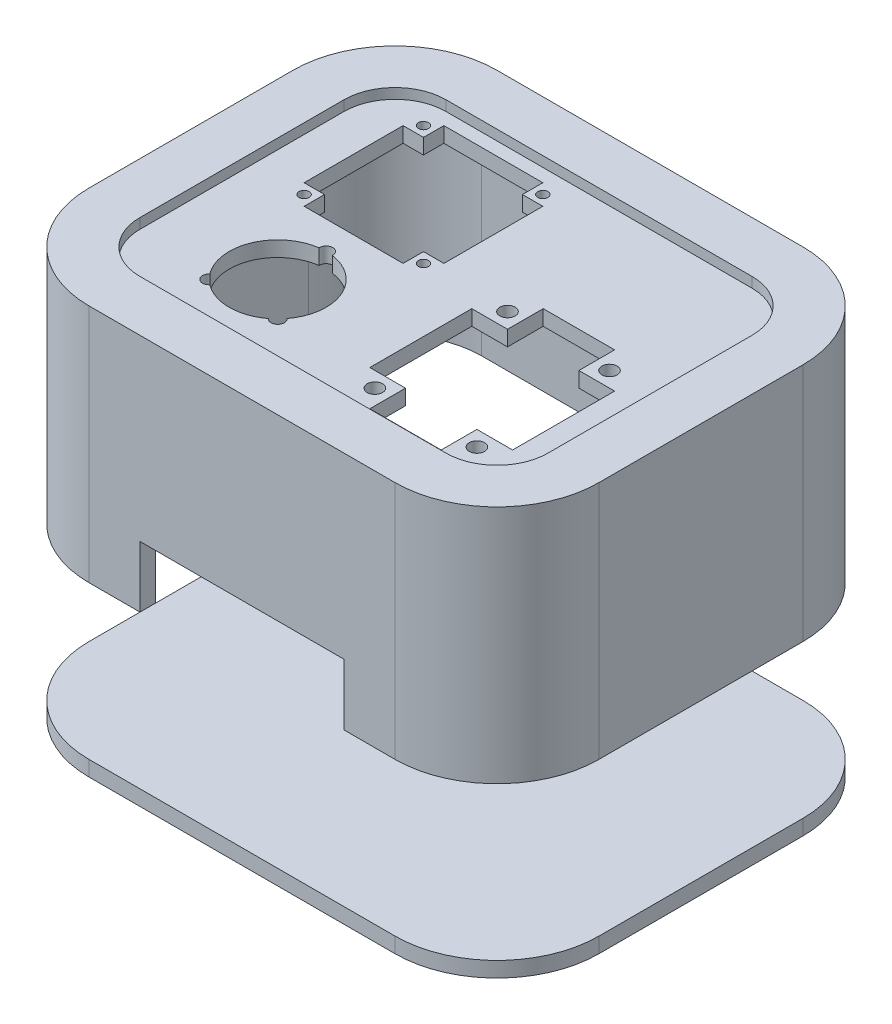
SolidWorks part; units mm, degrees
note: The reader was unsure of these and kept them because the rebuilt part matched: shared geometry of "草图2<6>", "草图2<8>", "草图9<7>", "草图9<8>", "草图9<9>", "草图9<10>", "草图9<11>", "草图9<12>", "草图9<13>".
ref_plane "前视基准面" through (0, 0, 0) normal (0, 0, 1) x (1, 0, 0)
ref_plane "上视基准面" through (0, 0, 0) normal (0, 1, 0) x (1, 0, 0)
ref_plane "右视基准面" through (0, 0, 0) normal (1, 0, 0) x (0, 0, -1)
sketch "草图1" plane through (0, 0, 0) normal (0, 1, 0) x (1, 0, 0)
  line L0 (10, 0) -> (70, 0)
  line L1 (80, 10) -> (80, 50)
  line L2 (70, 60) -> (10, 60)
  line L3 (0, 50) -> (0, 10)
  arc A0 (0, 50) -> (10, 60) centre (10, 50) cw
  arc A1 (80, 50) -> (70, 60) centre (70, 50) ccw
  arc A2 (70, 0) -> (80, 10) centre (70, 10) ccw
  arc A3 (10, 0) -> (0, 10) centre (10, 10) cw
  point P7 (0, 60)
  point P12 (80, 0)
  point P15 (0, 0)
  dimension "D3" = 10
  dimension "D4" = 10
  dimension "D5" = 10
  dimension "D6" = 10
  dimension "D1" = 80
  dimension "D2" = 60
extrude "拉伸-薄壁1" add sketch "草图1" along normal blind 60 thin contours L3 A3 L0 A2 L1 A1 L2 A0
sketch "草图2" plane through (0, 60, 0) normal (0, 1, 0) x (1, 0, 0)
  line L5 (10, 0) -> (70, 0)
  line L6 (0, 10) -> (0, 50)
  line L7 (10, 60) -> (70, 60)
  line L8 (80, 10) -> (80, 50)
  arc A0 (70, 60) -> (80, 50) centre (70, 50) cw
  arc A1 (0, 50) -> (10, 60) centre (10, 50) cw
  arc A2 (10, 0) -> (0, 10) centre (10, 10) cw
  arc A3 (70, 0) -> (80, 10) centre (70, 10) ccw
  point P12 (0, 0)
  dimension "D1" = 10
extrude "凸台-拉伸1" add sketch "草图2" against normal blind 10 contours L6 A1 L7 A0 L8 A3 L5 A2
sketch "草图3" plane through (0, 60, 0) normal (0, 1, 0) x (1, 0, 0)
  line L0 (0, 0) -> (50, 0)
  line L8 (67, 2.0583) -> (53, 2.0583)
  line L9 (53, 9.0583) -> (51.1362, 9.0583)
  line L10 (71, 29.0583) -> (67, 29.0583)
  line L11 (67, 6.0583) -> (67, 2.0583)
  line L12 (67, 29.0583) -> (67, 32.2378)
  line L13 (51, 29.0583) -> (53, 29.0583)
  line L14 (46, 9.0583) -> (51.1362, 9.0583)
  line L15 (53, 29.0583) -> (53, 31)
  line L16 (67, 6.0583) -> (67, 9.0583)
  line L17 (46, 29.0583) -> (51, 29.0583)
  line L18 (46, 9.0583) -> (46, 29.0583)
  line L19 (53, 3.67) -> (53, 9.0583)
  line L21 (53, 36.0583) -> (53, 31)
  line L24 (67, 36.0583) -> (67, 32.2378)
  line L25 (53, 36.0583) -> (67, 36.0583)
  line L29 (74, 9.0583) -> (71.1362, 9.0583)
  line L32 (74, 29.0583) -> (71, 29.0583)
  line L33 (74, 9.0583) -> (74, 29.0583)
  line L34 (71.1362, 9.0583) -> (67, 9.0583)
  line L36 (53, 3.67) -> (53, 2.0583)
  circle A0 centre (70, 6.0583) radius 1.5
  circle A1 centre (50, 6.0583) radius 1.5
  circle A2 centre (50, 32.0583) radius 1.5
  circle A3 centre (70, 32.0583) radius 1.5
  point P36 (53, 6.3642)
  dimension "D1" = 3
  dimension "D2" = 20
  dimension "D3" = 20
  dimension "D4" = 26
  dimension "D5" = 3
  dimension "D6" = 3
  dimension "D7" = 7
  dimension "D8" = 7
  dimension "D9" = 3
  dimension "D10" = 3
  dimension "D11" = 3
  dimension "D12" = 3
  dimension "D13" = 7
  dimension "D14" = 7
extrude "切除-拉伸2" cut sketch "草图2<6>" against normal blind 2
sketch "草图2<6>" plane through (0, 60, 0) normal (0, 1, 0) x (1, 0, 0) same geometry as "草图2"
extrude "切除-拉伸5" cut sketch "草图3" against normal through all contours A1 | A3 | A2 | L19 L36 L8 L11 L16 L34 L29 L33 L32 L10 L12 L24 L25 L21 L15 L13 L17 L18 L14 L9 | A0
sketch "草图6" plane through (0, 58, 0) normal (0, 1, 0) x (1, 0, 0)
  line L0 (0, 0) -> (22, 0)
  line L1 (10, 0) -> (70, 0) construction
  arc A0 (16.2625, 7.4283) -> (27.7375, 7.4283) centre (22, 15) ccw
  arc A1 (23.297, 24.4111) -> (20.703, 24.4111) centre (22, 24.5) ccw
  arc A2 (14.4283, 9.2625) -> (16.2625, 7.4283) centre (15.2825, 8.2825) ccw
  arc A3 (27.7375, 7.4283) -> (29.5717, 9.2625) centre (28.7175, 8.2825) ccw
  arc A4 (29.5717, 9.2625) -> (23.297, 24.4111) centre (22, 15) ccw
  arc A5 (20.703, 24.4111) -> (14.4283, 9.2625) centre (22, 15) ccw
  dimension "D1" = 15
extrude "切除-拉伸6" cut sketch "草图6" against normal through all contours A1 A5 A2 A0 A3 A4
sketch "草图7" plane through (0, 58, 0) normal (0, 1, 0) x (1, 0, 0)
  line L0 (0, 0) -> (22, 0)
  line L2 (31.5849, 32) -> (31.5849, 30)
  line L3 (31.5849, 32) -> (31.5849, 34)
  line L4 (31.5849, 34) -> (35.5849, 34)
  line L9 (31.5849, 30) -> (12.1849, 30)
  line L10 (35.5849, 34) -> (35.5849, 53.4)
  line L11 (31.5849, 57.4) -> (12.1849, 57.4)
  line L12 (8.1849, 34) -> (8.1849, 53.4)
  line L14 (12.1849, 32) -> (12.1849, 30)
  line L15 (12.1849, 30) -> (12.1849, 34)
  line L16 (12.1849, 34) -> (8.1849, 34)
  line L18 (10.1849, 53.4) -> (8.1849, 53.4)
  line L19 (8.1849, 53.4) -> (12.1849, 53.4)
  line L20 (12.1849, 53.4) -> (12.1849, 57.4)
  line L22 (31.5849, 55.4) -> (31.5849, 57.4)
  line L23 (31.5849, 57.4) -> (31.5849, 53.4)
  line L24 (31.5849, 53.4) -> (35.5849, 53.4)
  circle A0 centre (33.5849, 32) radius 1
  circle A1 centre (10.1849, 32) radius 1
  circle A2 centre (33.5849, 55.4) radius 1
  circle A3 centre (10.1849, 55.4) radius 1
  dimension "D5" = 2
  dimension "D1" = 30
  dimension "D2" = 2
  dimension "D3" = 2
  dimension "D4" = 2
  dimension "D6" = 2
  dimension "D7" = 2
  dimension "D8" = 2
  dimension "D9" = 2
extrude "切除-拉伸7" cut sketch "草图7" against normal through all contours L24 L23 L22 L11 L20 L19 L18 L12 L16 L15 L14 L9 L2 L3 L4 L10 | A0 | A3 | A2 | A1
sketch "草图8" plane through (0, 0, 10) normal (0, 0, 1) x (1, 0, 0)
  line L0 (0, 0) -> (10, 0)
  line L1 (10, 0) -> (70, 0) construction
  line L2 (10, 0) -> (20, 0)
  line L4 (20, 0) -> (60, 0)
  line L5 (20, 0) -> (20, 25)
  line L6 (20, 25) -> (60, 25)
  line L7 (60, 0) -> (60, 25)
  line M5 (10, 0) -> (70, 0)
extrude "切除-拉伸8" cut sketch "草图8" against normal blind 10 contours L7 L6 L5 M5
sketch "草图9" plane through (0, 0, 0) normal (0, -1, 0) x (1, 0, 0)
  line L1 (10, 0) -> (70, 0)
  line L2 (0, -10) -> (0, -50)
  line L3 (10, -60) -> (70, -60)
  line L4 (80, -10) -> (80, -50)
  arc A0 (0, -10) -> (10, 0) centre (10, -10) cw
  arc A1 (0, -50) -> (10, -60) centre (10, -50) ccw
  arc A2 (70, -60) -> (80, -50) centre (70, -50) ccw
  arc A3 (70, 0) -> (80, -10) centre (70, -10) cw
  point P7 (0, 0)
  dimension "D1" = 10
extrude "凸台-拉伸2" add sketch "草图9" along normal blind 10 from offset 10 separate body contours L2 A1 L3 A2 L4 A3 L1 A0
sketch "草图10" plane through (0, 0, 0) normal (0, -1, 0) x (1, 0, 0)
  line L1 (10, 0) -> (70, 0)
  line L2 (0, -10) -> (0, -50)
  line L3 (10, -60) -> (70, -60)
  line L4 (80, -10) -> (80, -50)
  arc A0 (80, -10) -> (70, 0) centre (70, -10) ccw
  arc A1 (70, -60) -> (80, -50) centre (70, -50) ccw
  arc A2 (0, -50) -> (10, -60) centre (10, -50) ccw
  arc A3 (0, -10) -> (10, 0) centre (10, -10) cw
  point P13 (0, 0)
  dimension "D1" = 10
extrude "拉伸-薄壁5" add sketch "草图10" along normal blind 10 from offset 10 thin contours L2 A2 L3 A1 L4 A0 L1 A3
extrude "切除-拉伸10" cut sketch "草图2<8>" against normal blind 10 from offset 5 offset against normal yes
sketch "草图2<8>" plane through (0, 60, 0) normal (0, 1, 0) x (1, 0, 0) same geometry as "草图2"
sketch "草图11" plane through (0, -10, 0) normal (0, 1, 0) x (1, 0, 0)
extrude "切除-拉伸-薄壁3" cut sketch "草图9<7>" against normal blind 55 thin thin type mid plane wall 10
sketch "草图9<7>" plane through (0, 0, 0) normal (0, -1, 0) x (1, 0, 0) same geometry as "草图9"
extrude "切除-拉伸-薄壁4" cut sketch "草图9<8>" along normal blind 5 from offset 10 thin
sketch "草图9<8>" plane through (0, 0, 0) normal (0, -1, 0) x (1, 0, 0) same geometry as "草图9"
extrude "切除-拉伸12" cut sketch "草图9<9>" along normal blind 5 from offset 10
sketch "草图9<9>" plane through (0, 0, 0) normal (0, -1, 0) x (1, 0, 0) same geometry as "草图9"
extrude "切除-拉伸-薄壁5" cut sketch "草图9<10>" against normal blind 55 thin thin type one direction wall 7
sketch "草图9<10>" plane through (0, 0, 0) normal (0, -1, 0) x (1, 0, 0) same geometry as "草图9"
extrude "切除-拉伸-薄壁6" cut sketch "草图9<11>" against normal blind 13 thin
sketch "草图9<11>" plane through (0, 0, 0) normal (0, -1, 0) x (1, 0, 0) same geometry as "草图9"
extrude "切除-拉伸13" cut sketch "草图9<12>" along normal blind 7 from offset 10
sketch "草图9<12>" plane through (0, 0, 0) normal (0, -1, 0) x (1, 0, 0) same geometry as "草图9"
extrude "切除-拉伸-薄壁7" cut sketch "草图9<13>" along normal blind 17 thin
sketch "草图9<13>" plane through (0, 0, 0) normal (0, -1, 0) x (1, 0, 0) same geometry as "草图9"
